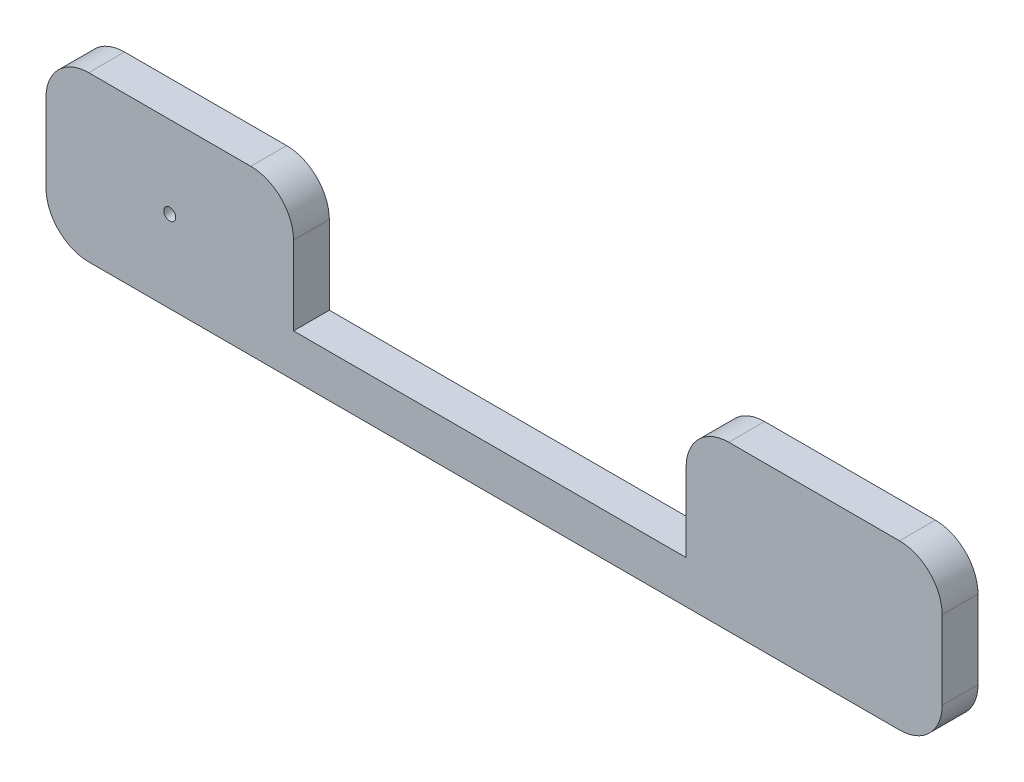
SolidWorks part; units mm, degrees
ref_plane "Front Plane" through (0, 0, 0) normal (0, 0, 1) x (1, 0, 0)
ref_plane "Top Plane" through (0, 0, 0) normal (0, 1, 0) x (1, 0, 0)
ref_plane "Right Plane" through (0, 0, 0) normal (1, 0, 0) x (0, 0, -1)
sketch "Sketch1" plane through (0, 0, 0) normal (0, 0, 1) x (1, 0, 0)
  line L1 (-85.0624, -35.0708) -> (48.2876, -35.0708)
  line L2 (-85.0624, -35.0708) -> (-85.0624, -59.4548)
  line L3 (-85.0624, -59.4548) -> (48.2876, -59.4548)
  line L4 (48.2876, -35.0708) -> (48.2876, -59.4548)
  dimension "D1" = 133.35
  dimension "D2" = 24.384
extrude "Boss-Extrude1" add sketch "Sketch1" along normal blind 5.334
sketch "Sketch3" plane through (0, 0, 5.334) normal (0, 0, 1) x (1, 0, 0)
  line L0 (48.2876, -35.0708) -> (-85.0624, -35.0708) construction
  line L1 (-48.2324, -35.0708) -> (10.1876, -35.0708)
  line L2 (-48.2324, -35.0708) -> (-48.2324, -53.1048)
  line L3 (-48.2324, -53.1048) -> (10.1876, -53.1048)
  line L4 (10.1876, -35.0708) -> (10.1876, -53.1048)
  line L5 (48.2876, -59.4548) -> (48.2876, -35.0708) construction
  dimension "D1" = 38.1
  dimension "D2" = 58.42
  dimension "D3" = 18.034
extrude "Cut-Extrude1" cut sketch "Sketch3" against normal through all
fillet "Fillet1" radius 6.35 6 edges at (-85.0624, -35.0708, 2.667) (-48.2324, -35.0708, 2.667) (10.1876, -35.0708, 2.667) (48.2876, -35.0708, 2.667) (48.2876, -59.4548, 2.667) (-85.0624, -59.4548, 2.667)
sketch "Sketch4" plane through (0, 0, 5.334) normal (0, 0, 1) x (1, 0, 0)
  line L1 (-85.0624, -47.2628) -> (-69.9279, -47.2628) construction
  line L2 (-85.0624, -41.4208) -> (-85.0624, -53.1048) construction
  line L3 (-66.6474, -35.0708) -> (-66.6474, -42.5901) construction
  line L4 (-54.5824, -35.0708) -> (-78.7124, -35.0708) construction
  circle A0 centre (-66.6474, -47.2628) radius 0.889
  dimension "D1" = 1.778
  dimension "D2" = 0
  dimension "D3" = 0
extrude "Cut-Extrude2" cut sketch "Sketch4" against normal through all
equation "\"MDF\"= .21in"
equation "\"Foamcore\"= .13in"
equation "\"Gmaterial\"= \"MDF\""
equation "\"D2@Sketch1\"=\"MDF\"+.25+.5"
equation "\"D1@Boss-Extrude1\"=\"MDF\""
equation "\"D3@Sketch3\"=\"MDF\"+.5"
